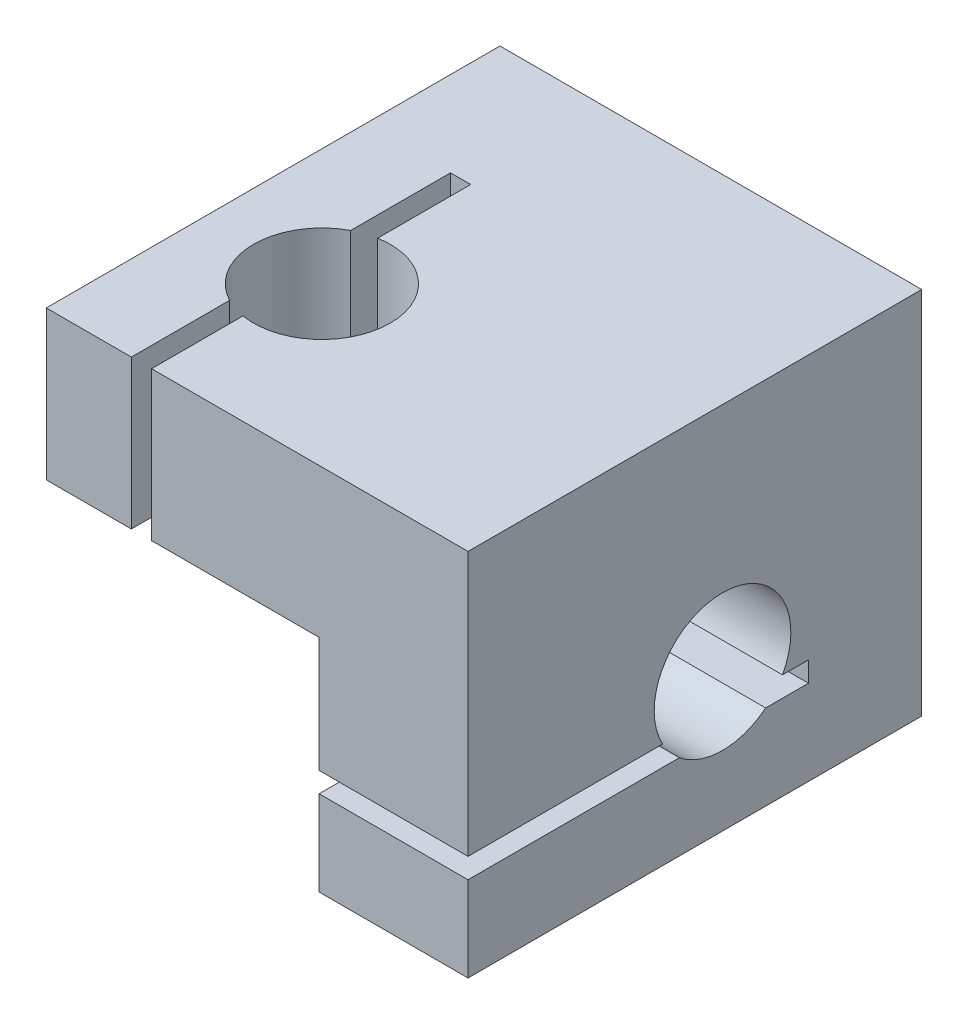
SolidWorks part; units mm, degrees
material "Rubber"
ref_plane "Front Plane" through (0, 0, 0) normal (0, 0, 1) x (1, 0, 0)
ref_plane "Top Plane" through (0, 0, 0) normal (0, 1, 0) x (1, 0, 0)
ref_plane "Right Plane" through (0, 0, 0) normal (1, 0, 0) x (0, 0, -1)
sketch "Sketch1" plane through (0, 0, 0) normal (0, 0, 1) x (1, 0, 0)
  line L1 (0, 0) -> (14, 0)
  line L2 (0, 0) -> (0, -34.73)
  line L3 (0, -34.73) -> (14, -34.73)
  line L4 (14, 0) -> (14, -34.73)
  line L5 (0, 0) -> (-25.65, 0)
  line L6 (0, 0) -> (0, -14)
  line L7 (0, -14) -> (-25.65, -14)
  line L8 (-25.65, 0) -> (-25.65, -14)
  dimension "D1" = 14
  dimension "D2" = 39.65
  dimension "D3" = 34.73
extrude "Boss-Extrude1" add sketch "Sketch1" along normal blind 42.65 contours L5 L8 L7 L2 | L4 L1 L2 L3 region at (7, -17.365, 0) region at (-12.825, -7, 0)
sketch "Sketch2" plane through (0, -14, 0) normal (0, -1, 0) x (1, 0, 0)
  line L0 (-25.65, 42.65) -> (-25.65, 0) construction
  line L1 (0, 42.65) -> (-25.65, 42.65) construction
  circle A0 centre (-14.665, 27.725) radius 6.425
  point P2 (-21.09, 27.725)
  point P6 (-14.665, 34.15)
  dimension "D1" = 12.85
  dimension "D2" = 4.56
  dimension "D3" = 8.5
extrude "Cut-Extrude1" cut sketch "Sketch2" against normal blind 42.65
sketch "Sketch3" plane through (0, -14, 0) normal (0, -1, 0) x (1, 0, 0)
  line L0 (0, 42.65) -> (-25.65, 42.65) construction
  line L1 (-17.65, 42.65) -> (-15.75, 42.65)
  line L2 (-17.65, 42.65) -> (-17.65, 12.65)
  line L3 (-17.65, 12.65) -> (-15.75, 12.65)
  line L4 (-15.75, 42.65) -> (-15.75, 12.65)
  line L5 (-25.65, 42.65) -> (-25.65, 0) construction
  dimension "D1" = 8
  dimension "D2" = 1.9
  dimension "D3" = 30
extrude "Cut-Extrude2" cut sketch "Sketch3" against normal blind 42.65
sketch "Sketch4" plane through (0, 0, 0) normal (-1, 0, 0) x (0, 0, 1)
  line L0 (42.65, -34.73) -> (0, -34.73) construction
  line L1 (42.65, -14) -> (42.65, -34.73) construction
  circle A0 centre (18.725, -21.745) radius 6.425
  point P2 (25.15, -21.745)
  point P3 (18.725, -28.17)
  dimension "D1" = 12.85
  dimension "D2" = 6.56
  dimension "D3" = 17.5
extrude "Cut-Extrude3" cut sketch "Sketch4" against normal blind 42.65
sketch "Sketch5" plane through (0, 0, 0) normal (-1, 0, 0) x (0, 0, 1)
  line L0 (42.65, -14) -> (42.65, -34.73) construction
  line L1 (42.65, -26.73) -> (10.65, -26.73)
  line L2 (42.65, -26.73) -> (42.65, -24.83)
  line L3 (42.65, -24.83) -> (10.65, -24.83)
  line L4 (10.65, -26.73) -> (10.65, -24.83)
  line L5 (42.65, -34.73) -> (0, -34.73) construction
  dimension "D1" = 8
  dimension "D2" = 1.9
  dimension "D3" = 32
extrude "Cut-Extrude4" cut sketch "Sketch5" against normal blind 42.65
hole_wizard "M3x0.5 Tapped Hole1" positions "Sketch6" profile "Sketch8" tap size "M3x0.5" standard "ANSI Metric"
sketch "Sketch6" plane through (0, 0, 0) normal (0, 0, -1) x (-1, 0, 0)
  line L0 (-14, 0) -> (25.65, 0) construction
  line L1 (25.65, 0) -> (25.65, -14) construction
  line L2 (-14, 0) -> (-14, -34.73) construction
  point P0 (1.1, -5.25)
  point P2 (13.5, -5.25)
  point P4 (-6.99, -21.8)
  dimension "D1" = 12.4
  dimension "D2" = 5.25
  dimension "D3" = 12.15
  dimension "D4" = 7.01
  dimension "D5" = 21.8
  dimension "D6" = 16.55
  dimension "D7" = 8.09
cosmetic thread "Hole Thread1" parameters "D1"=42.38, "D2"=3
cosmetic thread "Hole Thread2" parameters "D1"=42.38, "D2"=3
cosmetic thread "Hole Thread3" parameters "D1"=42.38, "D2"=3
sketch "Sketch8" plane through (-1.1, -5.25, 0) normal (1, 0, 0) x (0, 1, 0)
  line L0 (0, 0) -> (0, 10.7511)
  line L1 (0, 10.7511) -> (1.25, 10)
  line L2 (1.25, 10) -> (1.25, 0.275)
  line L3 (1.25, 0.275) -> (1.525, 0)
  line L5 (1.525, 0) -> (0, 0)
  line L6 (-1.25, 0.275) -> (-1.525, 0) construction
  line L10 (0, 10.7511) -> (-1.25, 10) construction
  line L11 (0, -6.35) -> (0, 107.95) construction
  dimension "Tap Drill Dia." = 2.5
  dimension "Tap Drill Depth" = 10
  dimension "Near C'Sink Dia." = 3.05
  dimension "Near C'Sink Angle" = 90
  dimension "Drill Angle" = 118
ref_axis "Axis1" through (-14.665, 0.9766, 27.725) along (0, -1, 0)
ref_point "Point1"
ref_plane "Plane2" through (-14.665, 0, 0) normal (-1, 0, 0) x (0, 0, 1)
ref_point "Point2"
ref_plane "Plane3" through (0, 0, 18.725) normal (0, 0, -1) x (-1, 0, 0)
